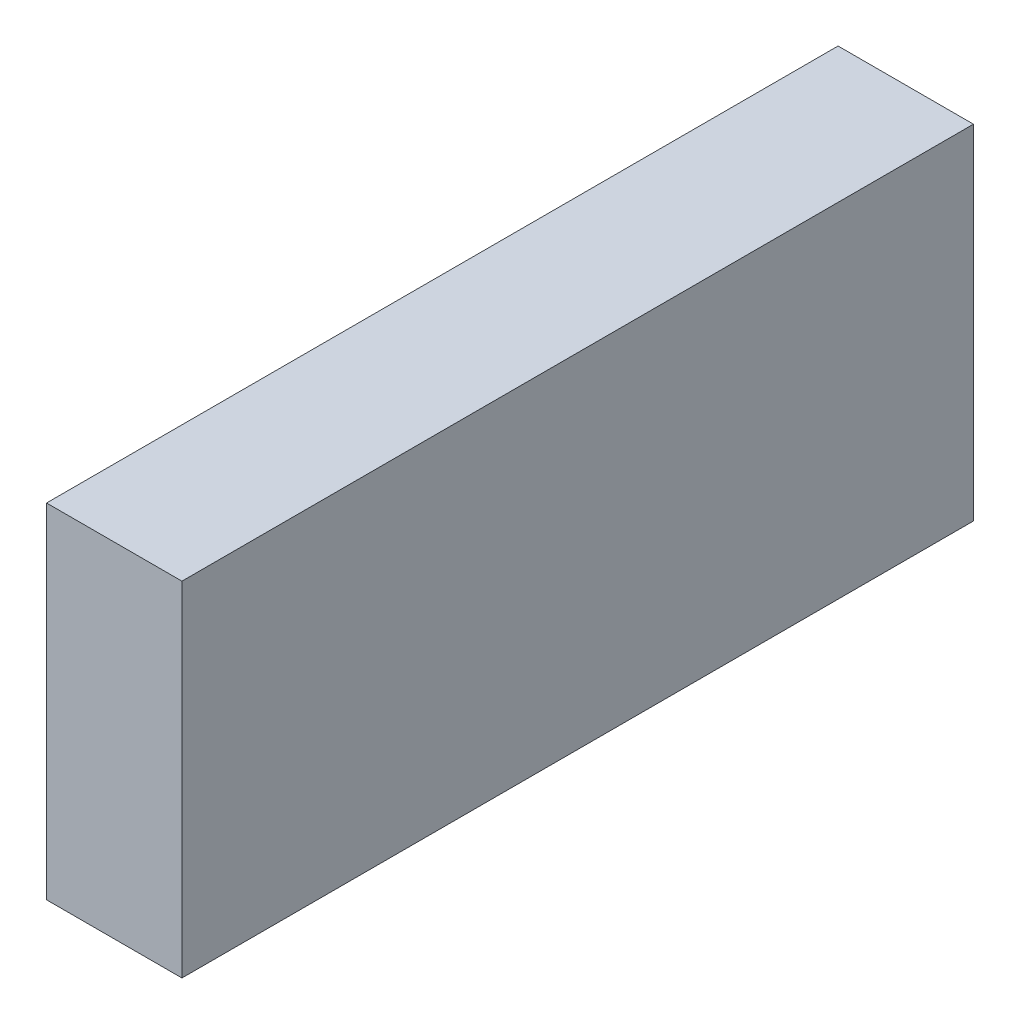
SolidWorks part; units mm, degrees
ref_plane "Front Plane" through (0, 0, 0) normal (0, 0, 1) x (1, 0, 0)
ref_plane "Top Plane" through (0, 0, 0) normal (0, 1, 0) x (1, 0, 0)
ref_plane "Right Plane" through (0, 0, 0) normal (1, 0, 0) x (0, 0, -1)
sketch "Case Sketch" plane through (0, 0, 0) normal (1, 0, 0) x (0, 0, -1)
  line L0 (38, -41) -> (38, -8)
  line L1 (38, -8) -> (-38, -8)
  line L2 (-38, -8) -> (-38, -41)
  line L3 (-38, -41) -> (38, -41)
extrude "Case" add sketch "Case Sketch" against normal blind 13
ref_axis "Engine Axis" through (0.65, 0, 0) along (-1, 0, 0)
